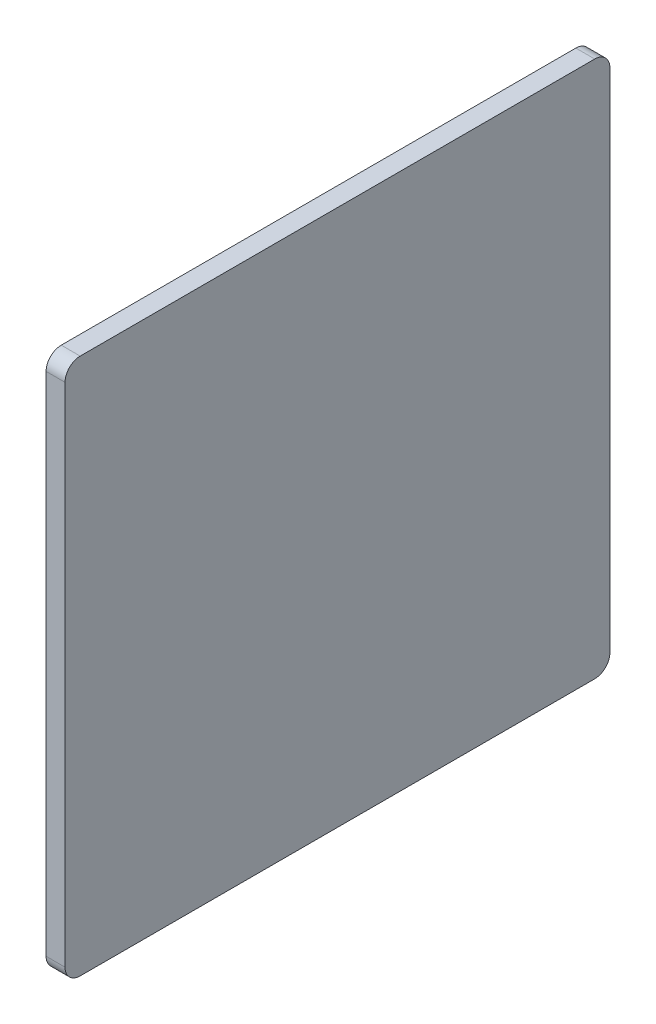
SolidWorks part; units mm, degrees
material "Acrylic (Medium-high impact)"
ref_plane "Front Plane" through (0, 0, 0) normal (0, 0, 1) x (1, 0, 0)
ref_plane "Top Plane" through (0, 0, 0) normal (0, 1, 0) x (1, 0, 0)
ref_plane "Right Plane" through (0, 0, 0) normal (1, 0, 0) x (0, 0, -1)
sketch "Sketch1" plane through (0, 0, 0) normal (1, 0, 0) x (0, 0, -1)
  line L1 (45.675, -45) -> (-45.675, -45)
  line L2 (45.675, -45) -> (45.675, 45)
  line L3 (45.675, 45) -> (-45.675, 45)
  line L4 (-45.675, -45) -> (-45.675, 45)
  line L5 (45.675, -45) -> (-45.675, 45) construction
  line L6 (45.675, 45) -> (-45.675, -45) construction
  point P0 (0, 0)
  dimension "D1" = 91.35
  dimension "D2" = 90
extrude "Boss-Extrude1" add sketch "Sketch1" along normal blind 3.175
fillet "Fillet1" radius 2.54 4 edges at (1.5875, -45, 45.675) (1.5875, -45, -45.675) (1.5875, 45, -45.675) (1.5875, 45, 45.675)
